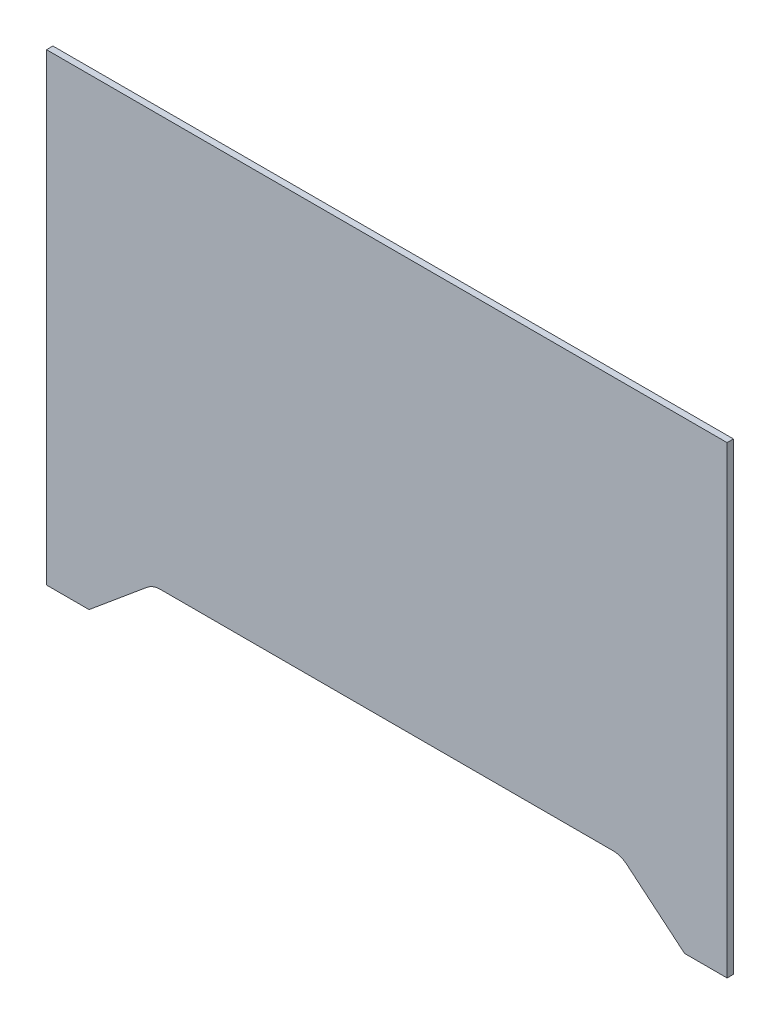
SolidWorks part; units mm, degrees
ref_plane "前视基准面" through (0, 0, 0) normal (0, 0, 1) x (1, 0, 0)
ref_plane "上视基准面" through (0, 0, 0) normal (0, 1, 0) x (1, 0, 0)
ref_plane "右视基准面" through (0, 0, 0) normal (1, 0, 0) x (0, 0, -1)
sketch "Sketch1" plane through (0, 0, 0) normal (0, 0, 1) x (1, 0, 0)
  line L0 (0, -109) -> (0, 0) construction
  line L1 (-160, -109) -> (160, -109) construction
  line L2 (-160, -109) -> (-160, 109)
  line L3 (-160, 109) -> (160, 109)
  line L4 (160, -109) -> (160, 109)
  line L5 (-160, -109) -> (160, 109) construction
  line L6 (-160, 109) -> (160, -109) construction
  line L7 (-106.3795, -84) -> (106.3795, -84)
  line L8 (112.7813, -86.3178) -> (140, -109)
  line L9 (140, -109) -> (160, -109)
  line L10 (-140, -109) -> (-160, -109)
  line L11 (-112.7813, -86.3178) -> (-140, -109)
  arc A0 (112.7813, -86.3178) -> (106.3795, -84) centre (106.3795, -94) ccw
  arc A1 (-112.7813, -86.3178) -> (-106.3795, -84) centre (-106.3795, -94) cw
  point P0 (0, 0)
  point P13 (110, -84)
  point P18 (0, -84)
  dimension "D6" = 10
  dimension "D1" = 320
  dimension "D2" = 218
  dimension "D3" = 25
  dimension "D4" = 20
  dimension "D5" = 110
extrude "Boss-Extrude1" add sketch "Sketch1" along normal blind 3
